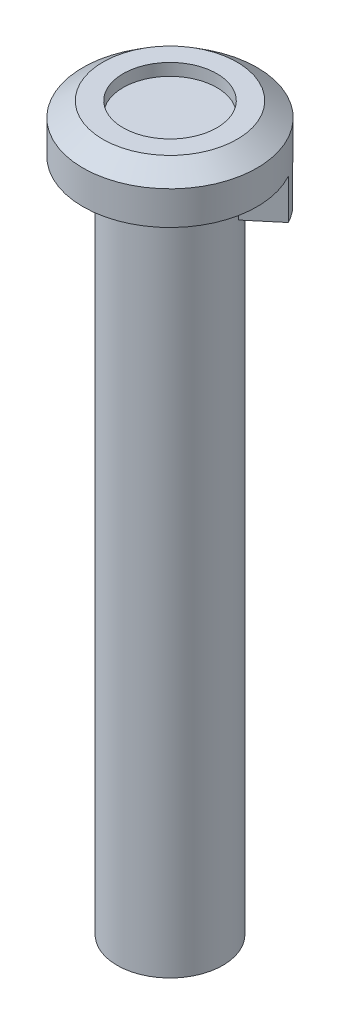
SolidWorks part; units mm, degrees
note: '?' marks a value the reader was unsure of.
ref_plane "Front Plane" through (0, 0, 0) normal (0, 0, 1) x (1, 0, 0)
ref_plane "Top Plane" through (0, 0, 0) normal (0, 1, 0) x (1, 0, 0)
ref_plane "Right Plane" through (0, 0, 0) normal (1, 0, 0) x (0, 0, -1)
ref_axis "Axis_X" through (-7.15, 0, 0) along (1, 0, 0)?
ref_axis "Axis_Y" through (0, 6.295, 0) along (0, -1, 0)
ref_axis "Axis_Z" through (0, 0, -7.15) along (0, 0, 1)?
sketch "Sketch1" plane through (0, 0, 0) normal (0, 0, 1) x (1, 0, 0)
  line L0 (0, 0) -> (0, -50.3) construction
  line L1 (0, 0) -> (3.95, 0)
  line L2 (3.95, 0) -> (3.95, -50.3)
  line L3 (3.95, -50.3) -> (0, -50.3)
  line L4 (0, -50.3) -> (0, 0)
  dimension "MSM_2" = 7.9
  dimension "MSM_1" = 50.3
revolve "Revolve1" add sketch "Sketch1" angle 360 about axis through (0, 6.295, 0) along (0, -1, 0)
cosmetic thread "Thread1" parameters "FIX_2"=6.647
sketch "Sketch2" plane through (0, 0, 0) normal (0, 0, 1) x (1, 0, 0)
  line L0 (0, 2.7) -> (0, 0) construction
  line L1 (0, 0) -> (6.5, 0)
  line L2 (6.5, 0) -> (6.5, 2.5)
  line L3 (6.5, 2.5) -> (5, 3.6)
  line L4 (5, 3.6) -> (3.5, 3.6)
  line L5 (3.5, 3.6) -> (3.5, 2.7)
  line L6 (3.5, 2.7) -> (0, 2.7)
  line L7 (0, 2.7) -> (0, 0)
  dimension "FIX_3" = 13
  dimension "FIX_4" = 7
  dimension "FIX_5" = 3.6
  dimension "FIX_6" = 0.9
  dimension "FIX_7" = 10
  dimension "FIX_8" = 1.1
revolve "Revolve2" add sketch "Sketch2" angle 360 about axis through (0, 6.295, 0) along (0, -1, 0)
ref_plane "Plane1" through (0, 0, 0) normal (0.6428, 0, 0.766) x (0, -1, 0)
sketch "Sketch3" plane through (0, 0, 0) normal (0.6428, 0, 0.766) x (0.766, 0, -0.6428)
  line L0 (0, 0) -> (6.5, 0)
  line L1 (6.5, 0) -> (0, -6.5)
  line L2 (0, -6.5) -> (0, 0)
  line L3 (-3.95, 0) -> (3.95, 0) construction
  dimension "FIX_11" = 135
extrude "Boss-Extrude1" add sketch "Sketch3" against normal blind 1.25
sketch "Sketch4" plane through (0, 0, 0) normal (0.6428, 0, 0.766) x (0.766, 0, -0.6428)
  line L1 (6.5, 0) -> (0, 0)
  line L2 (6.5, 0) -> (6.5, -3)
  line L3 (6.5, -3) -> (0, -3)
  line L4 (0, 0) -> (0, -3)
  dimension "FIX_13" = 3
extrude "Boss-Extrude2" add sketch "Sketch4" along normal blind 1.25
sketch "Sketch5" plane through (0, 3.6, 0) normal (0, 1, 0) x (1, 0, 0)
  circle A0 centre (0, 0) radius 6.5
  circle A1 centre (0, 0) radius 6.5 construction
extrude "Cut-Extrude1" cut sketch "Sketch5" against normal through all flip side to cut
sketch "Sketch6" plane through (0, -50.3, 0) normal (0, -1, 0) x (1, 0, 0)
  circle A0 centre (0, 0) radius 4.95
  circle A1 centre (0, 0) radius 3.95
  circle A2 centre (0, 0) radius 3.95 construction
  dimension "FIX_15" = 9.9
extrude "Cut-Extrude2" [suppressed] cut sketch "Sketch6" against normal blind 14
cosmetic thread "Thread2" [suppressed] parameters "FIX_18"=10, "FIX_17"=8.376
sketch "Sketch7" plane through (0, 0, 0) normal (0, 1, 0) x (1, 0, 0)
  line L1 (-8.45, -8.45) -> (8.45, -8.45) construction
  line L2 (-8.45, -8.45) -> (-8.45, 8.45) construction
  line L3 (-8.45, 8.45) -> (8.45, 8.45) construction
  line L4 (8.45, -8.45) -> (8.45, 8.45) construction
  line L5 (-8.45, -8.45) -> (8.45, 8.45) construction
  line L6 (-8.45, 8.45) -> (8.45, -8.45) construction
  line L7 (-4.9636, -8.45) -> (4.9636, -8.45)
  line L8 (-8.45, -4.9636) -> (-8.45, 4.9636)
  line L9 (-4.9636, 8.45) -> (4.9636, 8.45)
  line L10 (8.45, -4.9636) -> (8.45, 4.9636)
  line L11 (-8.45, -8.45) -> (8.45, 8.45) construction
  line L12 (-8.45, 8.45) -> (8.45, -8.45) construction
  circle A0 centre (0, 0) radius 9.8 construction
  arc A1 (-8.45, -4.9636) -> (-4.9636, -8.45) centre (0, 0) ccw
  arc A2 (-4.9636, 8.45) -> (-8.45, 4.9636) centre (0, 0) ccw
  arc A3 (8.45, 4.9636) -> (4.9636, 8.45) centre (0, 0) ccw
  arc A4 (4.9636, -8.45) -> (8.45, -4.9636) centre (0, 0) ccw
  point P0 (0, 0)
  dimension "FIX_20" = 19.6
  dimension "FIX_19" = 16.9
extrude "Boss-Extrude3" [suppressed] add sketch "Sketch7" along normal blind 5
sketch "Sketch8" [suppressed] plane through (0, 0, 0) normal (0, 0, 1) x (1, 0, 0)
  line L0 (0, 0) -> (-8.45, 0)
  line L1 (-8.45, 0) -> (-6.95, -2.5)
  line L2 (-6.95, -2.5) -> (0, -2.5)
  line L3 (0, -2.5) -> (0, 0)
  line L5 (-8.45, 5) -> (-8.45, 0) construction
  dimension "FIX_22" = 2.5
  dimension "FIX_23" = 1.5
extrude "Boss-Extrude4" [suppressed] add sketch "Sketch8" along normal mid plane 2.5
equation "\"Factor\"= 1.082532"
